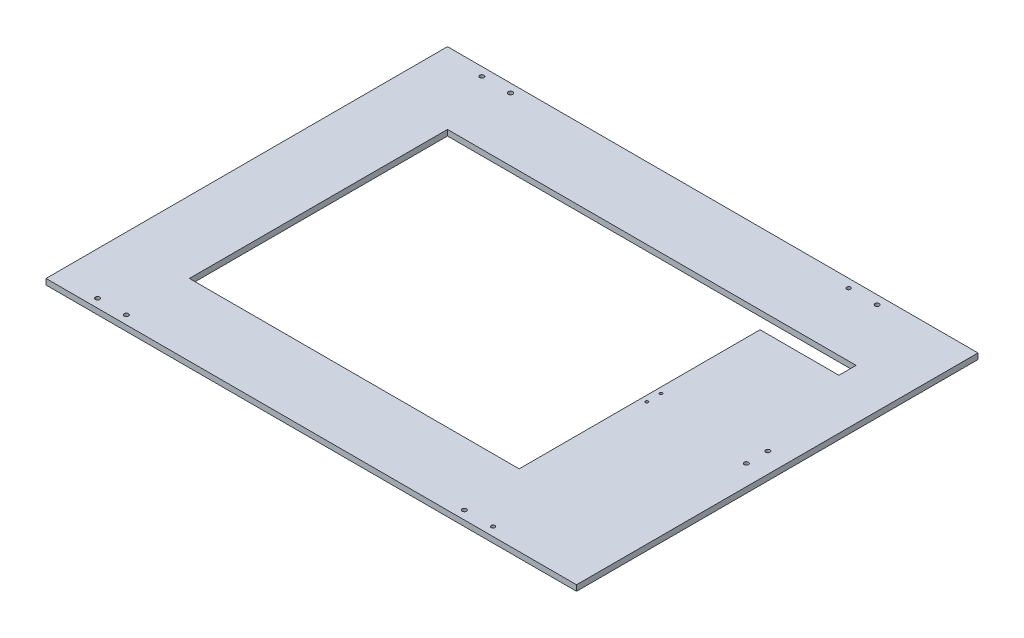
SolidWorks part; units mm, degrees
ref_plane "Front Plane" through (0, 0, 0) normal (0, 0, 1) x (1, 0, 0)
ref_plane "Top Plane" through (0, 0, 0) normal (0, 1, 0) x (1, 0, 0)
ref_plane "Right Plane" through (0, 0, 0) normal (1, 0, 0) x (0, 0, -1)
sketch "Sketch1" plane through (0, 0, 0) normal (0, 1, 0) x (1, 0, 0)
  line L1 (0, 0) -> (370, 0)
  line L2 (0, 0) -> (0, 280)
  line L3 (0, 280) -> (370, 280)
  line L4 (370, 0) -> (370, 280)
  line L5 (50, 50) -> (280, 50)
  line L6 (50, 50) -> (50, 230)
  line L7 (50, 230) -> (280, 230)
  line L8 (280, 50) -> (280, 230)
  line L9 (50, 280) -> (50, 274) construction
  line L10 (50, 274) -> (30, 274) construction
  line L12 (185, 280) -> (185, 0) construction
  line L13 (0, 140) -> (370, 140) construction
  line L14 (284, 140) -> (284, 145) construction
  line L15 (284, 140) -> (284, 135) construction
  circle A0 centre (30, 274) radius 1.5
  circle A1 centre (50, 274) radius 1.5692
  circle A2 centre (30, 6) radius 1.5
  circle A3 centre (50, 6) radius 1.5
  circle A4 centre (285.7569, 273.9854) radius 1.3573
  circle A5 centre (305.7569, 273.9346) radius 1.5
  circle A6 centre (285.7569, 6.0015) radius 1.5
  circle A7 centre (305.7569, 6.0068) radius 1.3225
  circle A8 centre (284, 145) radius 1
  circle A9 centre (284, 135) radius 1
  dimension "D11" = 3
  dimension "D12" = 2
  dimension "D1" = 370
  dimension "D2" = 280
  dimension "D3" = 230
  dimension "D4" = 50
  dimension "D5" = 50
  dimension "D6" = 50
  dimension "D8" = 6
  dimension "D10" = 20
  dimension "D13" = 4
  dimension "D14" = 10
  dimension "D15" = 20
  dimension "D16" = 20
  dimension "D17" = 20
extrude "Boss-Extrude1" add sketch "Sketch1" along normal blind 4
sketch "Sketch2" plane through (0, 4, 0) normal (0, 1, 0) x (1, 0, 0)
  line L1 (280, 230) -> (335, 230)
  line L2 (280, 230) -> (280, 218)
  line L3 (280, 218) -> (335, 218)
  line L4 (335, 230) -> (335, 218)
  dimension "D1" = 55
  dimension "D2" = 12
extrude "Cut-Extrude1" cut sketch "Sketch2" against normal blind 10
sketch "Sketch3" plane through (0, 4, 0) normal (0, 1, 0) x (1, 0, 0)
  line L0 (356, 140) -> (356, 147.5) construction
  line L1 (370, 0) -> (370, 280) construction
  line L3 (356, 147.5) -> (356, 140) construction
  line L6 (356, 140) -> (356, 132.5) construction
  circle A0 centre (356, 147.5) radius 1.5
  circle A1 centre (356, 132.5) radius 1.5
  dimension "D1" = 3
  dimension "D2" = 3
  dimension "D3" = 14
  dimension "D4" = 15
extrude "Cut-Extrude2" cut sketch "Sketch3" against normal blind 10
